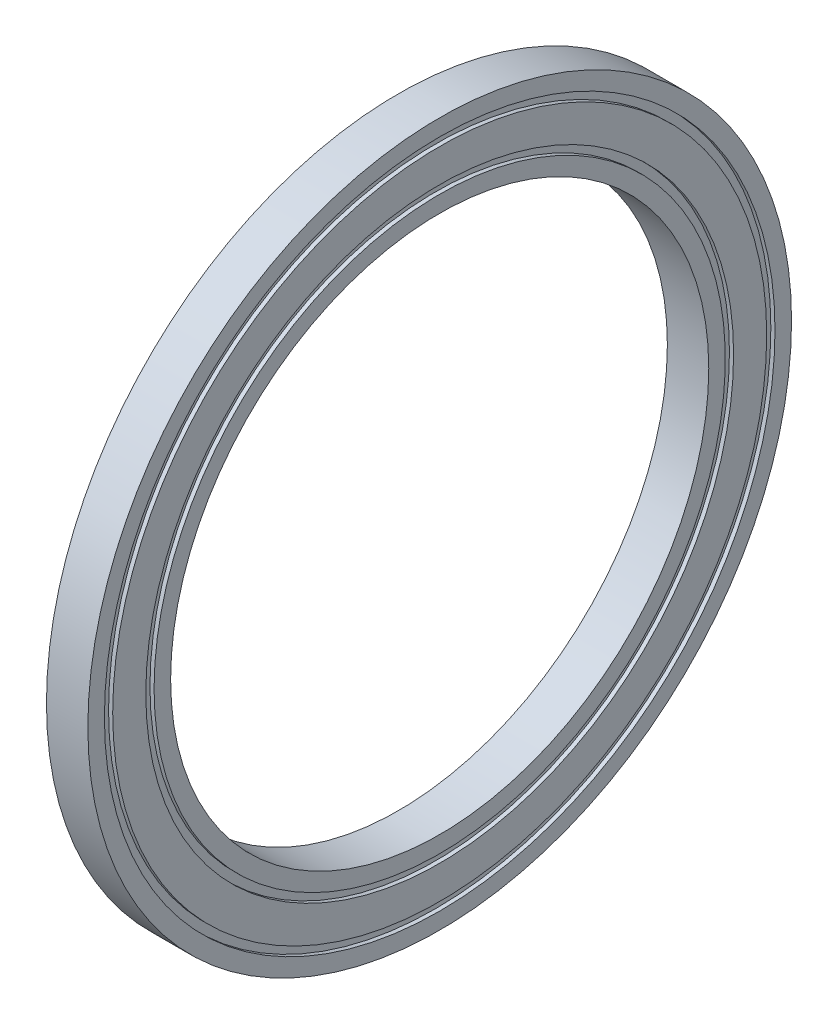
SolidWorks part; units mm, degrees
ref_plane "Front Plane" through (0, 0, 0) normal (0, 0, 1) x (1, 0, 0)
ref_plane "Top Plane" through (0, 0, 0) normal (0, 1, 0) x (1, 0, 0)
ref_plane "Right Plane" through (0, 0, 0) normal (1, 0, 0) x (0, 0, -1)
sketch "Sketch1" plane through (0, 0, 0) normal (0, 0, 1) x (1, 0, 0)
  line L0 (0, 0) -> (0, 32.5) construction
  line L1 (0, 32.5) -> (0, 42.5) construction
  line L2 (-2.5, 42.5) -> (2.5, 42.5)
  line L3 (2.5, 42.5) -> (2.5, 40.5)
  line L4 (2.5, 40.5) -> (2, 40.5)
  line L5 (2, 40.5) -> (2, 39.5)
  line L6 (2, 39.5) -> (2.5, 39.5)
  line L7 (2.5, 39.5) -> (2.5, 35.5)
  line L8 (2.5, 37.5) -> (0, 37.5) construction
  line L9 (2, 35.5) -> (2.5, 35.5)
  line L10 (2, 34.5) -> (2, 35.5)
  line L11 (2.5, 34.5) -> (2, 34.5)
  line L12 (2.5, 32.5) -> (2.5, 34.5)
  line L13 (-2.5, 32.5) -> (2.5, 32.5)
  line L14 (-2.5, 32.5) -> (-2.5, 34.5)
  line L15 (-2.5, 34.5) -> (-2, 34.5)
  line L16 (-2, 34.5) -> (-2, 35.5)
  line L17 (-2, 35.5) -> (-2.5, 35.5)
  line L18 (-2.5, 39.5) -> (-2.5, 35.5)
  line L19 (-2, 39.5) -> (-2.5, 39.5)
  line L20 (-2, 40.5) -> (-2, 39.5)
  line L21 (-2.5, 40.5) -> (-2, 40.5)
  line L22 (-2.5, 42.5) -> (-2.5, 40.5)
  line L23 (0, 0) -> (13.2088, 0) construction
  point P26 (0, 0)
  dimension "D1" = 5
  dimension "D2" = 2
  dimension "D3" = 0.5
  dimension "D4" = 5
  dimension "D5" = 2
  dimension "D6" = 2
  dimension "D7" = 37.5
revolve "Revolve1" add sketch "Sketch1" angle 360 about L23
